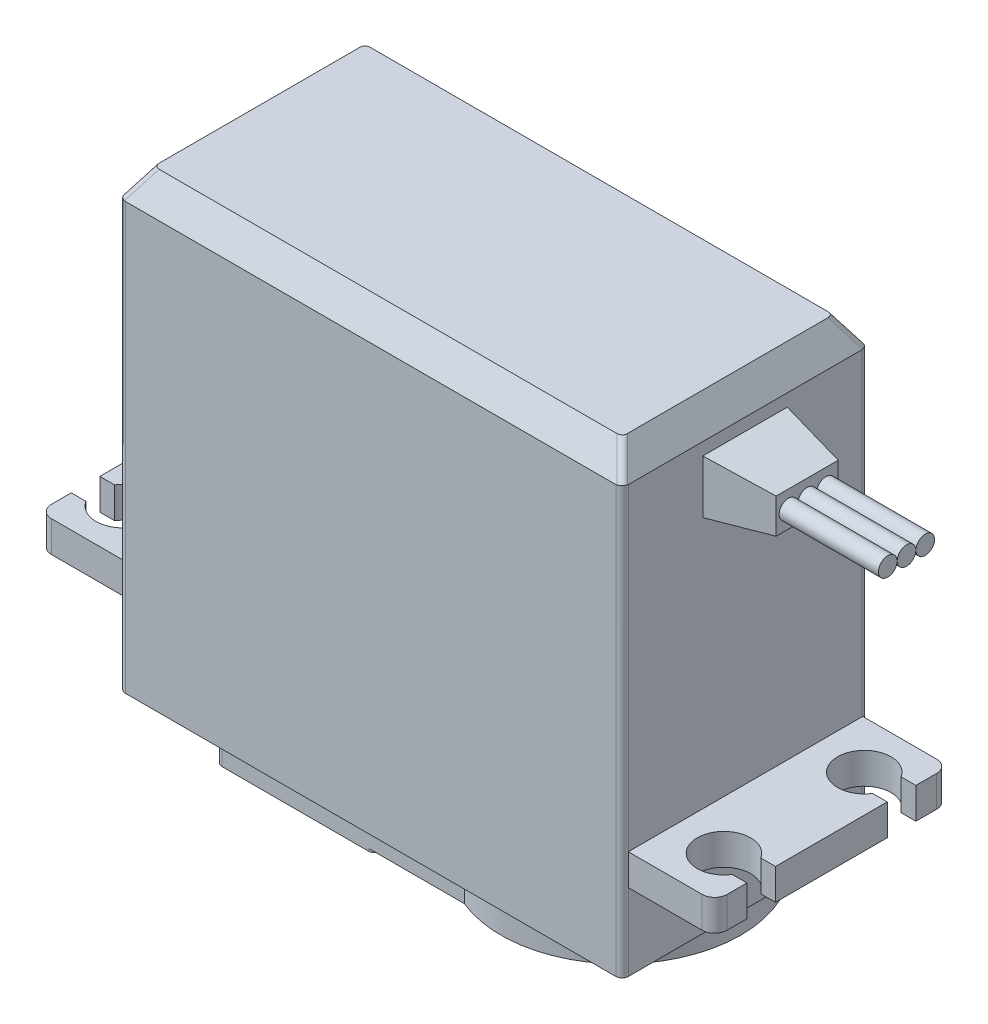
SolidWorks part; units mm, degrees
ref_plane "Front" through (0, 0, 0) normal (0, 0, 1) x (1, 0, 0)
ref_plane "Top" through (0, 0, 0) normal (0, 1, 0) x (1, 0, 0)
ref_plane "Right" through (0, 0, 0) normal (1, 0, 0) x (0, 0, -1)
sketch "Эскиз1" plane through (0, 0, 0) normal (0, 1, 0) x (1, 0, 0)
  line L1 (20.25, -9.9) -> (-20.25, -9.9)
  line L2 (20.25, -9.9) -> (20.25, 9.9)
  line L3 (20.25, 9.9) -> (-20.25, 9.9)
  line L4 (-20.25, -9.9) -> (-20.25, 9.9)
  line L5 (0, 9.9) -> (0, -9.9) construction
  line L6 (20.25, 0) -> (-20.25, 0) construction
  point P0 (0, 0)
  dimension "D1" = 19.8
  dimension "D2" = 40.5
extrude "Body" add sketch "Эскиз1" along normal blind 36.5
chamfer "Фаска1" distance 2.2 distance2 1.4 4 edges at (-20.25, 36.5, 0) (0, 36.5, -9.9) (20.25, 36.5, 0) (0, 36.5, 9.9) first distance on face at (-20.25, 18.25, 0) first distance on face at (0, 18.25, -9.9) first distance on face at (20.25, 18.25, 0) first distance on face at (0, 18.25, 9.9)
fillet "Скругление1" radius 0.5 8 edges at (-20.25, 17.15, -9.9) (-19.55, 35.4, -9.2) (19.55, 35.4, -9.2) (20.25, 17.15, -9.9) (19.55, 35.4, 9.2) (-19.55, 35.4, 9.2) (20.25, 17.15, 9.9) (-20.25, 17.15, 9.9)
ref_plane "Плоскость1" through (0, 6.2, 0) normal (0, -1, 0) x (-1, 0, 0)
sketch "Эскиз2" plane through (0, 6.2, 0) normal (0, -1, 0) x (-1, 0, 0)
  line L0 (-19.75, 9.9) -> (19.75, 9.9) construction
  line L1 (-26.2, 9.4728) -> (26.2, 9.4728)
  line L2 (27.2, -8.4) -> (27.2, -6.8)
  line L3 (-26.2, -9.4) -> (26.2, -9.4)
  line L4 (-27.2, -8.4) -> (-27.2, -6.8)
  line L5 (0, 9.9) -> (0, -9.9) construction
  line L6 (27.2, 0) -> (-27.2, 0) construction
  line L7 (-24.2, 5.65) -> (-27.2, 5.65) construction
  line L8 (-26.0166, 6.8) -> (-27.2, 6.8)
  line L9 (-26.0166, 4.5) -> (-27.2, 4.5)
  line L10 (-27.2, 6.8) -> (-27.2, 8.4728)
  line L11 (-26.0166, -4.5) -> (-27.2, -4.5)
  line L12 (-26.0166, -6.8) -> (-27.2, -6.8)
  line L13 (26.0166, -6.8) -> (27.2, -6.8)
  line L14 (26.0166, -4.5) -> (27.2, -4.5)
  line L15 (26.0166, 4.5) -> (27.2, 4.5)
  line L16 (26.0166, 6.8) -> (27.2, 6.8)
  line L17 (27.2, 6.8) -> (27.2, 8.4728)
  line L18 (27.2, -4.5) -> (27.2, 4.5)
  line L19 (-27.2, -4.5) -> (-27.2, 4.5)
  arc A0 (27.2, -8.4) -> (26.2, -9.4) centre (26.2, -8.4) cw
  arc A1 (26.2, 9.4728) -> (27.2, 8.4728) centre (26.2, 8.4728) cw
  arc A2 (-27.2, -8.4) -> (-26.2, -9.4) centre (-26.2, -8.4) ccw
  arc A3 (-27.2, 8.4728) -> (-26.2, 9.4728) centre (-26.2, 8.4728) cw
  arc A4 (-26.0166, 4.5) -> (-26.0166, 6.8) centre (-24.2, 5.65) ccw
  arc A5 (-26.0166, -4.5) -> (-26.0166, -6.8) centre (-24.2, -5.65) cw
  arc A6 (26.0166, -4.5) -> (26.0166, -6.8) centre (24.2, -5.65) ccw
  arc A7 (26.0166, 4.5) -> (26.0166, 6.8) centre (24.2, 5.65) cw
  point P0 (0, 0)
  point P10 (27.2, 9.9)
  point P16 (-27.2, 9.9)
  dimension "D2" = 1
  dimension "D4" = 4.3
  dimension "D1" = 54.4
  dimension "D5" = 3
  dimension "D6" = 1.15
extrude "Mount" add sketch "Эскиз2" against normal blind 2.5 contours L15 A7 L16 L17 A1 L1 A3 L10 L8 A4 L9 L4 L11 A5 L12 A2 L3 A0 L2 L13 A6 L14 L18 region at (0, 6.2, -0.039)
sketch "Эскиз3" plane through (0, 0, 0) normal (0, 0, 1) x (1, 0, 0)
  line L0 (-27.2, 6.2) -> (-20.25, 6.2)
  line L1 (-20.25, 6.2) -> (-20.25, 5.2)
  line L2 (-20.25, 0) -> (-20.25, 6.2) construction
  line L3 (-20.25, 5.2) -> (-27.2, 6.2)
  line L4 (0, 0) -> (0, 36.5) construction
  line L5 (-18.4282, 36.5) -> (18.4282, 36.5) construction
  line L6 (20.25, 5.2) -> (27.2, 6.2)
  line L7 (20.25, 6.2) -> (20.25, 5.2)
  line L8 (27.2, 6.2) -> (20.25, 6.2)
  dimension "D1" = 1
extrude "Бобышка-Вытянуть3" add sketch "Эскиз3" along normal mid plane 1
sketch "Эскиз4" plane through (0, 0, 0) normal (0, -1, 0) x (1, 0, 0)
  line L0 (20.25, 9.4) -> (20.25, -9.4) construction
  line L1 (-13.4526, -8.92) -> (-13.4526, -4.6)
  line L2 (-13.4526, -8.92) -> (6.5681, -8.92)
  line L3 (-13.4526, 8.92) -> (6.5681, 8.92)
  line L6 (-13.4526, 4.6) -> (-13.4526, 8.92)
  arc A0 (6.5681, -8.92) -> (6.5681, 8.92) centre (10.25, 0) ccw
  arc A1 (-13.4526, 4.6) -> (-13.4526, -4.6) centre (-11.493, 0) ccw
  point P2 (20.25, 0)
  point P6 (3.35, 0)
  dimension "D1" = 19.3
  dimension "D5" = 5
  dimension "D2" = 10
  dimension "D3" = 17.84
  dimension "D4" = 9.2
extrude "Бобышка-Вытянуть4" add sketch "Эскиз4" along normal blind 2
sketch "Эскиз5" plane through (0, -2, 0) normal (0, -1, 0) x (1, 0, 0)
  line L0 (-13.4526, -8.92) -> (6.5681, -8.92) construction
  line L1 (-13.4526, 8.92) -> (-0.6526, 8.92)
  line L2 (-13.4526, 8.92) -> (-13.4526, -8.92)
  line L3 (-13.4526, -8.92) -> (-0.6526, -8.92)
  line L4 (-0.6526, 8.92) -> (-0.6526, 2)
  line L5 (-0.6526, -2) -> (-0.6526, -8.92)
  line L7 (-1.6526, -7.92) -> (-12.4526, -7.92)
  line L8 (-1.6526, -7.92) -> (-1.6526, 7.92)
  line L9 (-1.6526, 7.92) -> (-12.4526, 7.92)
  line L10 (-12.4526, -7.92) -> (-12.4526, 7.92)
  line L11 (-7.0526, 7.92) -> (-7.0526, -7.92) construction
  line L12 (-1.6526, 0) -> (-12.4526, 0) construction
  arc A0 (-0.6526, 2) -> (-0.6526, -2) centre (-0.6526, 0) cw
  point P10 (-7.0526, 0)
  dimension "D2" = 2
  dimension "D1" = 12.8
  dimension "D3" = 1
  dimension "D4" = 15.84
  dimension "D5" = 10.8
extrude "Бобышка-Вытянуть5" add sketch "Эскиз5" along normal blind 0.2
sketch "Эскиз6" plane through (0, -2, 0) normal (0, -1, 0) x (1, 0, 0)
  circle A0 centre (10.25, 0) radius 6.6
  dimension "D1" = 13.2
extrude "Бобышка-Вытянуть6" add sketch "Эскиз6" along normal blind 1.2
sketch "Эскиз7" plane through (0, -3.2, 0) normal (0, -1, 0) x (1, 0, 0)
  circle A0 centre (10.25, 0) radius 5.35
  dimension "D1" = 10.7
extrude "Бобышка-Вытянуть7" add sketch "Эскиз7" along normal blind 0.5
sketch "Эскиз8" plane through (0, -3.7, 0) normal (0, -1, 0) x (1, 0, 0)
  circle A0 centre (10.25, 0) radius 2.6
  dimension "D1" = 5.2
extrude "Shaft hole" cut sketch "Эскиз8" against normal blind 10
fillet "Скругление2" radius 0.5 10 edges at (-13.4526, -1.1, 8.92) (-0.6526, -2.1, 2) (-0.6526, -2.1, -2) (-13.4526, -1.1, -8.92) (-1.6526, -2.1, 7.92) (-1.6526, -2.1, -7.92) (-12.4526, -2.1, 7.92) (-12.4526, -2.1, -7.92)
sketch "Эскиз9" plane through (20.25, 0, 0) normal (1, 0, 0) x (0, 0, -1)
  line L0 (-8.0782, 36.5) -> (8.0782, 36.5) construction
  line L1 (-3.4, 33.3) -> (3.4, 33.3)
  line L2 (-3.4, 33.3) -> (-3.4, 29)
  line L3 (-3.4, 29) -> (3.4, 29)
  line L4 (3.4, 33.3) -> (3.4, 29)
  line L5 (0, 29) -> (0, 33.3) construction
  line L6 (-3.4, 31.15) -> (3.4, 31.15) construction
  point P0 (0, 31.15)
  dimension "D1" = 3.2
  dimension "D2" = 6.8
  dimension "D3" = 4.3
ref_plane "Плоскость2" through (25.25, 0, 0) normal (1, 0, 0) x (0, 0, -1)
sketch "Эскиз10" plane through (25.25, 0, 0) normal (1, 0, 0) x (0, 0, -1)
  line L1 (-2.5, 29.75) -> (2.5, 29.75)
  line L2 (-2.5, 29.75) -> (-2.5, 32.55)
  line L3 (-2.5, 32.55) -> (2.5, 32.55)
  line L4 (2.5, 29.75) -> (2.5, 32.55)
  line L5 (0, 32.55) -> (0, 29.75) construction
  line L6 (-2.5, 31.15) -> (2.5, 31.15) construction
  point P0 (0, 31.15)
  dimension "D1" = 2.8
  dimension "D2" = 5
loft "Rubber" add profiles "Эскиз10", "Эскиз9" connector at (25.25, 32.55, 2.5) connector at (20.25, 33.3, 3.4)
sketch "Эскиз11" plane through (25.25, 0, 0) normal (1, 0, 0) x (0, 0, -1)
  circle A0 centre (0, 31.1505) radius 0.75
  circle A1 centre (1.51, 31.15) radius 0.75
  circle A2 centre (-1.51, 31.15) radius 0.75
  dimension "D1" = 1.5
  dimension "D2" = 1.51
  dimension "D3" = 1.51
extrude "Бобышка-Вытянуть10" add sketch "Эскиз11" along normal blind 8
